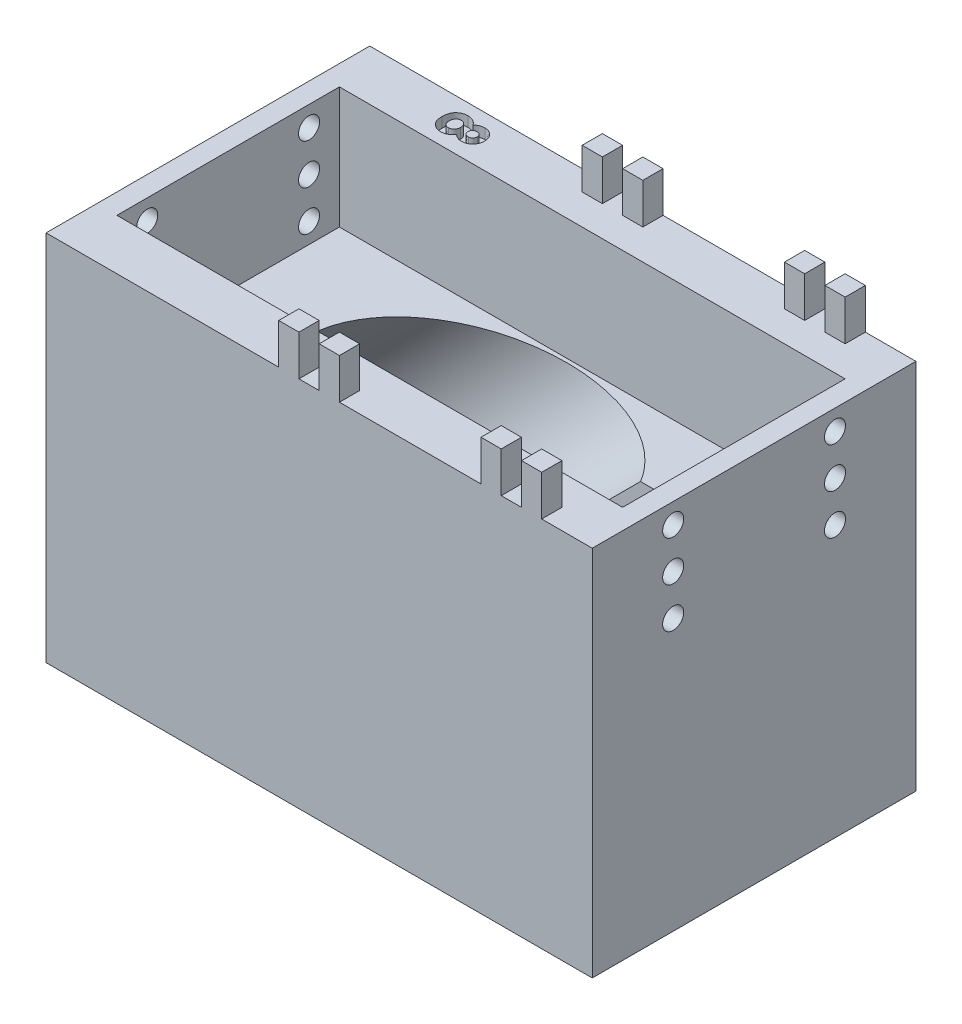
SolidWorks part; units mm, degrees
ref_plane "Front Plane" through (0, 0, 0) normal (0, 0, 1) x (1, 0, 0)
ref_plane "Top Plane" through (0, 0, 0) normal (0, 1, 0) x (1, 0, 0)
ref_plane "Right Plane" through (0, 0, 0) normal (1, 0, 0) x (0, 0, -1)
sketch "Sketch1" plane through (0, 0, 0) normal (0, 0, 1) x (1, 0, 0)
  line L1 (-139.7, -127) -> (88.9, -127)
  line L2 (-139.7, -127) -> (-139.7, 0)
  line L3 (-139.7, 0) -> (88.9, 0)
  line L4 (88.9, -127) -> (88.9, 0)
  line L5 (-139.7, -127) -> (88.9, 0) construction
  line L6 (-139.7, 0) -> (88.9, -127) construction
  point P0 (0, 0)
  dimension "D1" = 228.6
  dimension "D2" = 127
  dimension "D3" = 88.9
extrude "Boss-Extrude1" add sketch "Sketch1" along normal mid plane 101.6
sketch "Sketch10" plane through (0, -127, 0) normal (0, -1, 0) x (1, 0, 0)
  circle A0 centre (0, 0) radius 7.5
  dimension "D1" = 15
extrude "Cut-Extrude6" cut sketch "Sketch10" against normal through all
sketch "Sketch2" plane through (0, 0, 0) normal (0, 0, 1) x (1, 0, 0)
  line L0 (-124.923, -127.463) -> (0, -2.54) construction
  line L1 (-96.5908, -81.1703) -> (-99.8251, -77.9359)
  line L3 (-99.8251, -77.9359) -> (-111.4754, -66.2857)
  line L4 (-111.4754, -66.2857) -> (-47.7297, -2.54)
  line L5 (-50.1339, -52.6739) -> (-73.9987, -28.809) construction
  line L6 (-105.207, -107.747) -> (-129.2867, -131.8267)
  line L7 (0, -2.54) -> (59.728, 57.188)
  line L8 (-47.7297, -2.54) -> (0, -2.54) construction
  line L9 (-47.7297, -2.54) -> (0, 45.1897)
  line L10 (0, -2.54) -> (-105.207, -107.747)
  line L11 (88.9, 0) -> (-139.7, 0) construction
  line L12 (59.728, 57.188) -> (38.3281, 83.5178)
  line L13 (0, 45.1897) -> (0, -2.54) construction
  line L14 (-96.5908, -81.1703) -> (-189.3831, -173.9626)
  line L15 (-189.3831, -173.9626) -> (-180.4029, -182.9429)
  line L16 (-180.4029, -182.9429) -> (-129.2867, -131.8267)
  line L17 (38.3281, 83.5178) -> (0, 45.1897)
  point P23 (-50.1339, -52.6739)
  dimension "D1" = 45
  dimension "D2" = 53
  dimension "D3" = 2.54
  dimension "D4" = 70.9
  dimension "D6" = 33.75
  dimension "D9" = 12.7
revolve "Cut-Revolve1" cut sketch "Sketch2" angle 360 about L0
sketch "Sketch11" plane through (0, -127, 0) normal (0, -1, 0) x (1, 0, 0)
  line L1 (13, 13) -> (-13, 13)
  line L2 (13, 13) -> (13, -13)
  line L3 (13, -13) -> (-13, -13)
  line L4 (-13, 13) -> (-13, -13)
  line L5 (13, 13) -> (-13, -13) construction
  line L6 (13, -13) -> (-13, 13) construction
  point P0 (0, 0)
  dimension "D1" = 26
extrude "Cut-Extrude7" cut sketch "Sketch11" along normal blind 76.2 from surface starting at plane "Top Plane"
sketch "Sketch13" plane through (0, 0, 0) normal (0, 1, 0) x (1, 0, 0)
  line L0 (88.9, 50.8) -> (-139.7, 50.8) construction
  line L1 (-41.275, 50.8) -> (-34.925, 50.8)
  line L2 (-41.275, 50.8) -> (-41.275, 44.45)
  line L3 (-41.275, 44.45) -> (-34.925, 44.45)
  line L4 (-34.925, 50.8) -> (-34.925, 44.45)
  line L5 (0, 0) -> (42.9001, 0) construction
  line L6 (-28.575, 50.8) -> (-22.225, 50.8)
  line L7 (-28.575, 50.8) -> (-28.575, 44.45)
  line L8 (-28.575, 44.45) -> (-22.225, 44.45)
  line L9 (-22.225, 50.8) -> (-22.225, 44.45)
  line L10 (0, 0) -> (0, -29.3087) construction
  line L11 (22.225, 50.8) -> (22.225, 44.45)
  line L12 (28.575, 44.45) -> (22.225, 44.45)
  line L13 (28.575, 50.8) -> (28.575, 44.45)
  line L14 (28.575, 50.8) -> (22.225, 50.8)
  line L15 (34.925, 50.8) -> (34.925, 44.45)
  line L16 (41.275, 44.45) -> (34.925, 44.45)
  line L17 (41.275, 50.8) -> (41.275, 44.45)
  line L18 (41.275, 50.8) -> (34.925, 50.8)
  line L19 (41.275, -50.8) -> (34.925, -50.8)
  line L20 (41.275, -50.8) -> (41.275, -44.45)
  line L21 (41.275, -44.45) -> (34.925, -44.45)
  line L22 (34.925, -50.8) -> (34.925, -44.45)
  line L23 (28.575, -50.8) -> (22.225, -50.8)
  line L24 (28.575, -50.8) -> (28.575, -44.45)
  line L25 (28.575, -44.45) -> (22.225, -44.45)
  line L26 (22.225, -50.8) -> (22.225, -44.45)
  line L27 (-22.225, -50.8) -> (-22.225, -44.45)
  line L28 (-28.575, -44.45) -> (-22.225, -44.45)
  line L29 (-28.575, -50.8) -> (-28.575, -44.45)
  line L30 (-28.575, -50.8) -> (-22.225, -50.8)
  line L31 (-34.925, -50.8) -> (-34.925, -44.45)
  line L32 (-41.275, -44.45) -> (-34.925, -44.45)
  line L33 (-41.275, -50.8) -> (-41.275, -44.45)
  line L34 (-41.275, -50.8) -> (-34.925, -50.8)
  point P18 (-25.4, 50.8)
  point P20 (-38.1, 50.8)
  dimension "D1" = 25.4
  dimension "D2" = 12.7
  dimension "D3" = 6.35
extrude "Boss-Extrude3" add sketch "Sketch13" along normal blind 12.7
sketch "Sketch22" plane through (0, 0, 0) normal (0, 1, 0) x (1, 0, 0)
  line L0 (-41.275, -50.8) -> (-139.7, -50.8) construction
  line L1 (-139.7, 50.8) -> (-114.3, 50.8)
  line L2 (-139.7, 50.8) -> (-139.7, -50.8)
  line L3 (-139.7, -50.8) -> (-114.3, -50.8)
  line L4 (-114.3, 50.8) -> (-114.3, -50.8)
  dimension "D1" = 25.4
extrude "Cut-Extrude17" cut sketch "Sketch22" against normal through all
sketch "Sketch23" plane through (0, -127, 0) normal (0, -1, 0) x (1, 0, 0)
  line L0 (-127, 127) -> (127, -127) construction
  line L1 (-127, 127) -> (127, 127)
  line L2 (-127, 127) -> (-127, -127)
  line L3 (-127, -127) -> (127, -127)
  line L4 (127, 127) -> (127, -127)
  dimension "D1" = 254
  dimension "D2" = 254
extrude "Cut-Extrude18" cut sketch "Sketch23" against normal blind 10.16
sketch "Sketch21" plane through (0, 0, 0) normal (0, 1, 0) x (1, 0, 0)
  line L1 (88.9, -50.8) -> (57.15, -50.8)
  line L2 (88.9, -50.8) -> (88.9, 50.8)
  line L3 (88.9, 50.8) -> (57.15, 50.8)
  line L4 (57.15, -50.8) -> (57.15, 50.8)
  line L5 (88.9, -50.8) -> (41.275, -50.8) construction
  line L6 (88.9, 50.8) -> (41.275, 50.8) construction
  line L7 (-114.3, -50.8) -> (-114.3, 50.8) construction
  point P4 (55.8259, 50.8)
  dimension "D1" = 171.45
extrude "Cut-Extrude16" cut sketch "Sketch21" against normal through all
sketch "Sketch26" plane through (0, 0, 0) normal (0, 1, 0) x (1, 0, 0)
  line L0 (57.15, 50.8) -> (57.15, -50.8) construction
  line L1 (-107.95, -34.925) -> (50.8, -34.925)
  line L2 (-107.95, -34.925) -> (-107.95, 34.925)
  line L3 (-107.95, 34.925) -> (50.8, 34.925)
  line L4 (50.8, -34.925) -> (50.8, 34.925)
  line L5 (-114.3, -50.8) -> (-114.3, 50.8) construction
  point P4 (-107.95, 0)
  dimension "D1" = 6.35
  dimension "D2" = 6.35
  dimension "D3" = 69.85
extrude "Cut-Extrude21" cut sketch "Sketch26" against normal blind 38.1
sketch "Sketch27" plane through (-114.3, 0, 0) normal (-1, 0, 0) x (0, 0, 1)
  line L0 (50.8, 0) -> (-50.8, 0) construction
  line L1 (-25.4, -6.35) -> (25.4, -6.35) construction
  line L2 (-25.4, -6.35) -> (-25.4, -19.05) construction
  line L3 (-25.4, -19.05) -> (25.4, -19.05) construction
  line L4 (25.4, -6.35) -> (25.4, -19.05) construction
  line L7 (-25.4, -19.05) -> (-25.4, -31.75) construction
  line L8 (-25.4, -31.75) -> (25.4, -31.75) construction
  line L9 (25.4, -19.05) -> (25.4, -31.75) construction
  circle A0 centre (-25.4, -6.35) radius 3.302
  circle A1 centre (25.4, -6.35) radius 3.302
  circle A2 centre (25.4, -19.05) radius 3.302
  circle A3 centre (25.4, -31.75) radius 3.302
  circle A5 centre (-25.4, -19.05) radius 3.302
  circle A6 centre (-25.4, -31.75) radius 3.302
  point P4 (0, -6.35)
  dimension "D5" = 6.604
  dimension "D1" = 50.8
  dimension "D2" = 12.7
  dimension "D3" = 6.35
  dimension "D4" = 12.7
  dimension "D6" = 2
  dimension "D7" = 3
extrude "Cut-Extrude22" cut sketch "Sketch27" against normal through all both and the other way through all
sketch "Sketch28" plane through (0, 0, 0) normal (0, 1, 0) x (1, 0, 0)
  line L0 (-83.4499, 50.8) -> (-83.4499, 34.925) construction
  line L1 (-41.275, 50.8) -> (-114.3, 50.8) construction
  line L2 (50.8, 34.925) -> (-107.95, 34.925) construction
  text T0 "<b>8</b>" font "Century Gothic" height 12.7
extrude "Cut-Extrude23" cut sketch "Sketch28" against normal blind 3.175
